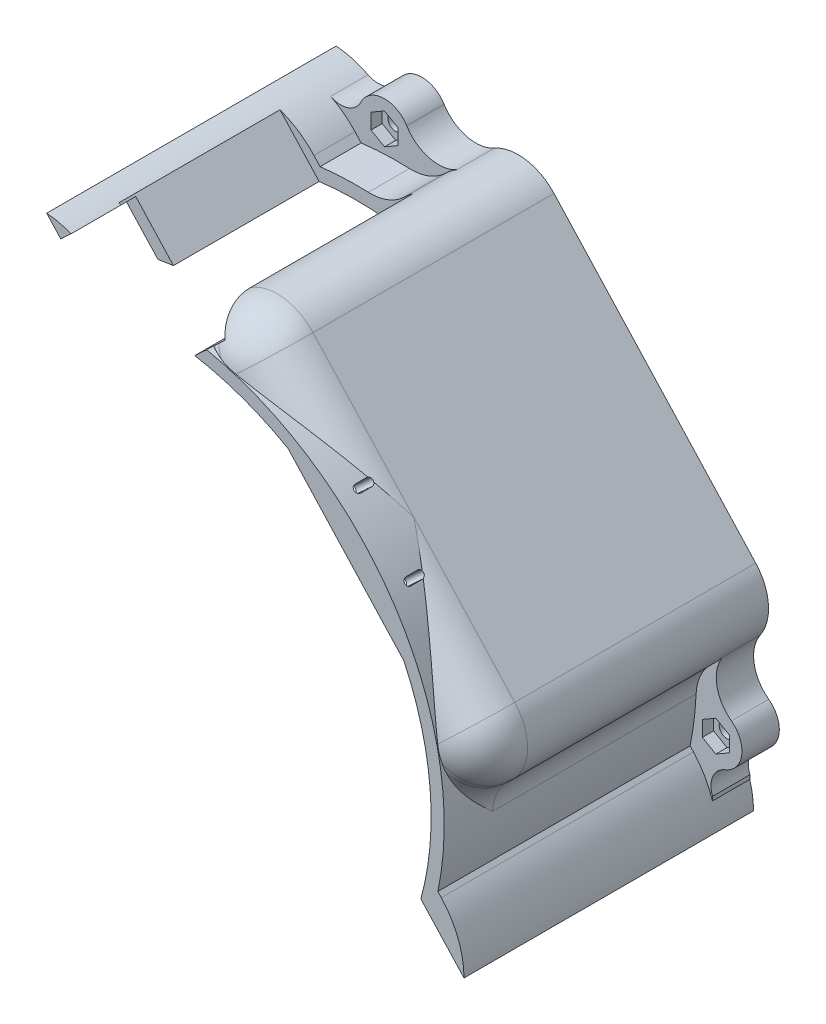
SolidWorks part; units mm, degrees
ref_plane "Front Plane" through (0, 0, 0) normal (0, 0, 1) x (1, 0, 0)
ref_plane "Top Plane" through (0, 0, 0) normal (0, 1, 0) x (1, 0, 0)
ref_plane "Right Plane" through (0, 0, 0) normal (1, 0, 0) x (0, 0, -1)
sketch "Sketch1" plane through (0, 0, 0) normal (0, 0, 1) x (1, 0, 0)
  circle A0 centre (0, 0) radius 80
  dimension "D1" = 160
extrude "Boss-Extrude1" add sketch "Sketch1" against normal blind 77.5
sketch "Sketch2" plane through (0, 0, 0) normal (0, 0, 1) x (1, 0, 0)
  line L0 (200.8326, -158.5296) -> (-139.7794, 211.8025)
  line L1 (94.6839, 15.2306) -> (23.0799, 93.0824) construction
  line L2 (20.979, 36.2785) -> (10.8247, 47.3189) construction
  line L3 (200.8326, -158.5296) -> (4.1016, -190.3864)
  line L4 (4.1016, -190.3864) -> (-214.9461, 22.8399)
  line L5 (-214.9461, 22.8399) -> (-139.7794, 211.8025)
  dimension "D1" = 0.5
extrude "Cut-Extrude1" cut sketch "Sketch2" against normal blind 136
sketch "Sketch3" plane through (0, 0, -77.5) normal (0, 0, -1) x (-1, 0, 0)
  line L0 (-94.6839, 15.2306) -> (-23.0799, 93.0824)
  line L1 (-23.0799, 93.0824) -> (-8.3778, 79.5601)
  line L2 (-8.3778, 79.5601) -> (-79.9818, 1.7083)
  line L3 (-79.9818, 1.7083) -> (-94.6839, 15.2306)
  arc A0 (16.8949, 78.1957) -> (-76.5128, -23.3623) centre (0, 0) ccw construction
extrude "Boss-Extrude3" add sketch "Sketch3" against normal up to vertex (77.5 mm away)
sketch "Sketch7" plane through (0, 0, 0) normal (0, 0, 1) x (1, 0, 0)
  line L0 (76.5128, -23.3623) -> (-16.8949, 78.1957)
  arc A0 (76.5128, -23.3623) -> (-16.8949, 78.1957) centre (0, 0) ccw
extrude "Boss-Extrude4" add sketch "Sketch7" against normal blind 30
fillet "Fillet4" radius 13 4 edges at (8.3778, 79.5601, -38.75) (79.9818, 1.7083, -38.75) (23.0799, 93.0824, -38.75) (94.6839, 15.2306, -38.75)
fillet "Fillet5" radius 13 9 edges at (81.1243, 1.4212, 0) (89.3038, 15.4555, 0) (22.855, 87.7023, 0) (8.187, 80.7227, 0) (78.8465, -13.5362, 0) (-6.9083, 79.7012, 0) (58.8819, 54.1565, 0) (84.6132, 5.9681, 0) (13.0092, 83.8199, 0)
sketch "Sketch8" plane through (0, 0, 0) normal (0, 0, 1) x (1, 0, 0)
  line L0 (76.5128, -23.3623) -> (-16.8949, 78.1957)
  line L1 (65.9406, -11.8676) -> (-6.3227, 66.701) construction
  arc A0 (76.5128, -23.3623) -> (-16.8949, 78.1957) centre (0, 0) ccw
extrude "Boss-Extrude5" add sketch "Sketch8" against normal blind 60
sketch "Sketch11" plane through (0, 0, -77.5) normal (0, 0, -1) x (-1, 0, 0)
  line L0 (-58.9016, -9.0027) -> (-85.2082, 15.1927)
  line L1 (-85.2082, 15.1927) -> (-22.2513, 83.6429)
  line L2 (-22.2513, 83.6429) -> (4.819, 58.745)
  line L3 (4.819, 58.745) -> (-58.9016, -9.0027)
  line L4 (-31.8803, 83.5141) -> (-85.8835, 24.7989) construction
  line L5 (-22.1922, 82.2299) -> (-83.7952, 15.2517) construction
  line L6 (-0.8475, 62.5982) -> (-22.1922, 82.2299) construction
  line L7 (-83.7952, 15.2517) -> (-62.4505, -4.38) construction
  dimension "D1" = 1
  dimension "D2" = 1
  dimension "D3" = 1
extrude "Cut-Extrude4" cut sketch "Sketch11" against normal blind 64
sketch "Sketch12" plane through (0, 0, -13.5) normal (0, 0, -1) x (-1, 0, 0)
  line L0 (-66.0171, 30.1494) -> (-73.1482, 22.3961)
  line L2 (-76.1885, 6.8968) -> (-57.9658, -9.8635)
  line L3 (-57.9658, -9.8635) -> (-41.7188, 7.8011)
  line L4 (-41.7188, 7.8011) -> (-66.0171, 30.1494)
  line L6 (-22.2513, 83.6429) -> (-85.2082, 15.1927) construction
  line L7 (-60.7468, 22.5848) -> (-65.899, 27.3235) construction
  line L8 (-65.899, 27.3235) -> (-74.0225, 18.4912) construction
  arc A2 (-73.1482, 22.3961) -> (-76.1885, 6.8968) centre (0, 0) ccw
  dimension "D3" = 153
  dimension "D1" = 2
  dimension "D2" = 2
extrude "Cut-Extrude5" cut sketch "Sketch12" against normal blind 59
sketch "Sketch13" plane through (-31.4784, 34.2251, 0) normal (0.677, -0.736, 0) x (0.736, 0.677, 0)
  line L0 (44, -56.5) -> (69, -56.5)
  line L1 (69, -56.5) -> (69, -13.5)
  line L2 (69, -13.5) -> (44, -13.5)
  line L3 (44, -13.5) -> (44, -56.5)
  line L4 (40.5, -77.5) -> (73, -77.5) construction
  line L5 (46, -54.5) -> (67, -54.5) construction
  line L6 (67, -54.5) -> (67, -16) construction
  line L7 (46, -16) -> (46, -54.5) construction
  line L9 (40.5, -13.5) -> (73, -13.5) construction
  dimension "D1" = 2
  dimension "D2" = 2
  dimension "D3" = 2
extrude "Cut-Extrude6" cut sketch "Sketch13" against normal blind 59
sketch "Sketch14" plane through (0, 0, 0) normal (0, 0, 1) x (1, 0, 0)
  line L1 (76.5128, -23.3623) -> (85.2898, -32.9051)
  line L2 (78.3166, -16.3253) -> (89.7732, -28.7815)
  line L3 (85.2898, -32.9051) -> (89.7732, -28.7815)
  line L6 (-16.8949, 78.1957) -> (-26.4079, 88.5388)
  line L7 (-9.7319, 79.4059) -> (-21.9245, 92.6624)
  line L8 (-26.4079, 88.5388) -> (-21.9245, 92.6624)
  arc A0 (76.5128, -23.3623) -> (-16.8949, 78.1957) centre (0, 0) ccw construction
  arc A1 (76.5128, -23.3623) -> (78.3166, -16.3253) centre (0, 0) ccw
  arc A2 (-9.7319, 79.4059) -> (-16.8949, 78.1957) centre (0, 0) ccw
extrude "Boss-Extrude7" add sketch "Sketch14" against normal up to vertex (77.5 mm away)
fillet "Fillet6" radius 23 2 edges at (-21.9245, 92.6624, -38.75) (89.7732, -28.7815, -38.75)
sketch "Sketch15" plane through (-31.4784, 34.2251, 0) normal (0.677, -0.736, 0) x (0.736, 0.677, 0)
  line L0 (44, -56.5) -> (69, -56.5)
  line L1 (44, -56.5) -> (44, -13.4286)
  line L2 (69, -56.5) -> (69, -13.4286)
  line L3 (44, -13.4286) -> (69, -13.4286)
extrude "Cut-Extrude7" cut sketch "Sketch15" against normal blind 59
sketch "Sketch16" plane through (0, 0, -13.5) normal (0, 0, -1) x (-1, 0, 0)
  line L0 (-66.0171, 30.1494) -> (-28.423, 71.0238)
  line L1 (-66.0171, 30.1494) -> (-73.1482, 22.3961) construction
  line L2 (1.6695, 61.6418) -> (-13.2316, 75.347)
  line L3 (1.6695, 61.6418) -> (-45.0405, 10.8562)
  line L4 (-45.0405, 10.8562) -> (-66.0171, 30.1494)
  arc A0 (-13.2316, 75.347) -> (-28.423, 71.0238) centre (0, 0) ccw
extrude "Cut-Extrude8" cut sketch "Sketch16" against normal blind 59
sketch "Sketch17" plane through (0, 0, -13.5) normal (0, 0, -1) x (-1, 0, 0)
  line L0 (-28.423, 71.0238) -> (-73.1482, 22.3961)
  arc A0 (-73.1482, 22.3961) -> (-28.423, 71.0238) centre (0, 0) ccw
extrude "Cut-Extrude9" cut sketch "Sketch17" against normal blind 59 and the other way blind 84
sketch "Sketch18" plane through (29.809, 27.4167, 0) normal (-0.736, -0.677, 0) x (0, 0, 1)
  line L0 (-17.5, 46.5) -> (-17.5, 77.5)
  line L1 (-17.5, 17.5) -> (-17.5, 90) construction
  line L2 (-17.5, 82.5) -> (0, 82.5) construction
  line L3 (-76.5, 46.5) -> (-15.5, 46.5) construction
  line L4 (-17.5, 77.5) -> (12.9519, 77.5)
  line L5 (12.9519, 77.5) -> (12.9519, 46.5)
  line L6 (12.9519, 46.5) -> (-17.5, 46.5)
  dimension "D1" = 5
  dimension "D2" = 0
extrude "Cut-Extrude11" cut sketch "Sketch18" against normal up to vertex
sketch "Sketch19" plane through (0, 0, -77.5) normal (0, 0, -1) x (-1, 0, 0)
  line L0 (-12.5068, 83.3578) -> (-13.5116, 84.2819) construction
  line L1 (9.7319, 79.4059) -> (11.3697, 81.1866) construction
  line L2 (-12.5068, 83.3578) -> (-13.5116, 84.2819)
  line L3 (9.7319, 79.4059) -> (11.3697, 81.1866)
  line L4 (-53.7297, 49.4178) -> (-35.0775, 32.2624) construction
  line L5 (-22.2513, 83.6429) -> (-85.2082, 15.1927) construction
  line L6 (-78.3166, -16.3253) -> (-79.9544, -18.106)
  line L7 (-84.1108, 5.506) -> (-85.1156, 6.4301)
  arc A0 (9.7843, 88.8519) -> (-2.4638, 89.4663) centre (3.491, 85.7867) ccw
  arc A1 (9.7843, 88.8519) -> (17.8929, 86.1283) centre (15.1785, 91.4791) ccw
  arc A2 (-15.9017, 86.0233) -> (-2.4638, 89.4663) centre (-10.9707, 94.723) ccw
  arc A3 (26.4079, 88.5388) -> (11.3697, 81.1866) centre (28.2982, 65.6166) ccw construction
  arc A5 (-13.5116, 84.2819) -> (-31.8803, 83.5141) centre (-22.312, 74.7136) ccw construction
  circle A6 centre (3.491, 85.7867) radius 2.1
  arc A7 (-12.5068, 83.3578) -> (-3.1883, 79.9364) centre (-3.7064, 92.9261) ccw construction
  arc A8 (9.7319, 79.4059) -> (-3.1883, 79.9364) centre (0, 0) ccw construction
  arc A9 (-13.5116, 84.2819) -> (-15.9017, 86.0233) centre (-22.312, 74.7136) ccw
  arc A10 (-12.5068, 83.3578) -> (-3.1883, 79.9364) centre (-3.7064, 92.9261) ccw
  arc A11 (9.7319, 79.4059) -> (-3.1883, 79.9364) centre (0, 0) ccw
  arc A12 (17.8929, 86.1283) -> (11.3697, 81.1866) centre (28.2982, 65.6166) ccw
  arc A13 (-84.3344, -25.0189) -> (-79.9544, -18.106) centre (-63.0258, -33.676) cw
  arc A14 (-78.3166, -16.3253) -> (-79.9236, -3.4944) centre (0, 0) cw
  arc A15 (-84.1108, 5.506) -> (-79.9236, -3.4944) centre (-92.9112, -4.0623) cw
  arc A16 (-85.1156, 6.4301) -> (-87.0503, 8.6666) centre (-76.3152, 15.9985) cw
  circle A17 centre (-85.196, -10.6388) radius 2.1
  arc A18 (-87.0503, 8.6666) -> (-89.3598, -5.0118) centre (-95.3081, 3.0267) cw
  arc A19 (-87.7252, -17.1658) -> (-84.3344, -25.0189) centre (-89.8932, -22.7605) cw
  arc A20 (-87.7252, -17.1658) -> (-89.3598, -5.0118) centre (-85.196, -10.6388) cw
  dimension "D1" = 14
  dimension "D2" = 12
  dimension "D3" = 20
extrude "Boss-Extrude8" add sketch "Sketch19" against normal blind 10
sketch "Sketch20" plane through (0, 0, -67.5) normal (0, 0, 1) x (1, 0, 0)
  line L1 (0.109, 87.8651) -> (-3.491, 89.9436)
  line L2 (-3.491, 89.9436) -> (-7.091, 87.8651)
  line L3 (-7.091, 87.8651) -> (-7.091, 83.7082)
  line L4 (-7.091, 83.7082) -> (-3.491, 81.6298)
  line L5 (-3.491, 81.6298) -> (0.109, 83.7082)
  line L6 (0.109, 83.7082) -> (0.109, 87.8651)
  line L7 (88.796, -8.5603) -> (85.196, -6.4818)
  line L8 (85.196, -6.4818) -> (81.596, -8.5603)
  line L9 (81.596, -8.5603) -> (81.596, -12.7172)
  line L10 (81.596, -12.7172) -> (85.196, -14.7957)
  line L11 (85.196, -14.7957) -> (88.796, -12.7172)
  line L12 (88.796, -12.7172) -> (88.796, -8.5603)
  circle A0 centre (-3.491, 85.7867) radius 3.6 construction
  circle A1 centre (85.196, -10.6388) radius 3.6 construction
extrude "Cut-Extrude12" cut sketch "Sketch20" against normal blind 3
sketch "Sketch21" plane through (50.7856, 46.71, 0) normal (-0.736, -0.677, 0) x (0, 0, 1)
  line L0 (-5.25, 9.9949) -> (-8.25, 9.9949) construction
  line L1 (-5.25, 8.9949) -> (-8.25, 8.9949)
  line L2 (-5.25, 10.9949) -> (-8.25, 10.9949)
  line L3 (0, 0) -> (-8.9261, 0) construction
  line L4 (0, -33.0341) -> (0, 33.0341) construction
  line L5 (-5.25, -9.9949) -> (-8.25, -9.9949) construction
  line L6 (-5.25, -8.9949) -> (-8.25, -8.9949)
  line L7 (-5.25, -10.9949) -> (-8.25, -10.9949)
  line L8 (0, 33.0341) -> (-13.5, 33.0341) construction
  arc A0 (-5.25, 8.9949) -> (-5.25, 10.9949) centre (-5.25, 9.9949) ccw
  arc A1 (-8.25, 10.9949) -> (-8.25, 8.9949) centre (-8.25, 9.9949) ccw
  arc A2 (-5.25, -8.9949) -> (-5.25, -10.9949) centre (-5.25, -9.9949) cw
  arc A3 (-8.25, -10.9949) -> (-8.25, -8.9949) centre (-8.25, -9.9949) cw
  point P2 (-6.75, 9.9949)
  point P13 (-6.75, -9.9949)
  point P21 (-6.75, 33.0341)
  dimension "D1" = 1
  dimension "D2" = 3
extrude "Cut-Extrude13" cut sketch "Sketch21" against normal blind 52
sketch "Sketch23" plane through (0, 0, -13.5) normal (0, 0, -1) x (-1, 0, 0)
  line L0 (-22.2513, 83.6429) -> (-85.2082, 15.1927) construction
  line L1 (-38.2446, 66.2541) -> (-69.2149, 32.5815)
  arc A0 (-69.2149, 32.5815) -> (-38.2446, 66.2541) centre (0, 0) ccw
extrude "Cut-Extrude15" cut sketch "Sketch23" against normal blind 74
sketch "Sketch24" plane through (0, 0, -77.5) normal (0, 0, -1) x (-1, 0, 0)
  line L0 (-79.9544, -18.106) -> (-79.2184, -17.3057) construction
  line L1 (-79.9544, -18.106) -> (-79.2184, -17.3057)
  arc A0 (-79.2184, -17.3057) -> (-85.2898, -32.9051) centre (-62.2898, -32.8757) ccw construction
  arc A1 (-79.9544, -18.106) -> (-84.3344, -25.0189) centre (-63.0258, -33.676) ccw construction
  arc A2 (-79.2184, -17.3057) -> (-84.2798, -26.1347) centre (-62.2898, -32.8757) ccw
  arc A3 (-79.9544, -18.106) -> (-84.3344, -25.0189) centre (-63.0258, -33.676) ccw
  arc A4 (-84.3344, -25.0189) -> (-84.2798, -26.1347) centre (143.5637, -14.4238) ccw
extrude "Boss-Extrude9" add sketch "Sketch24" against normal up to vertex
